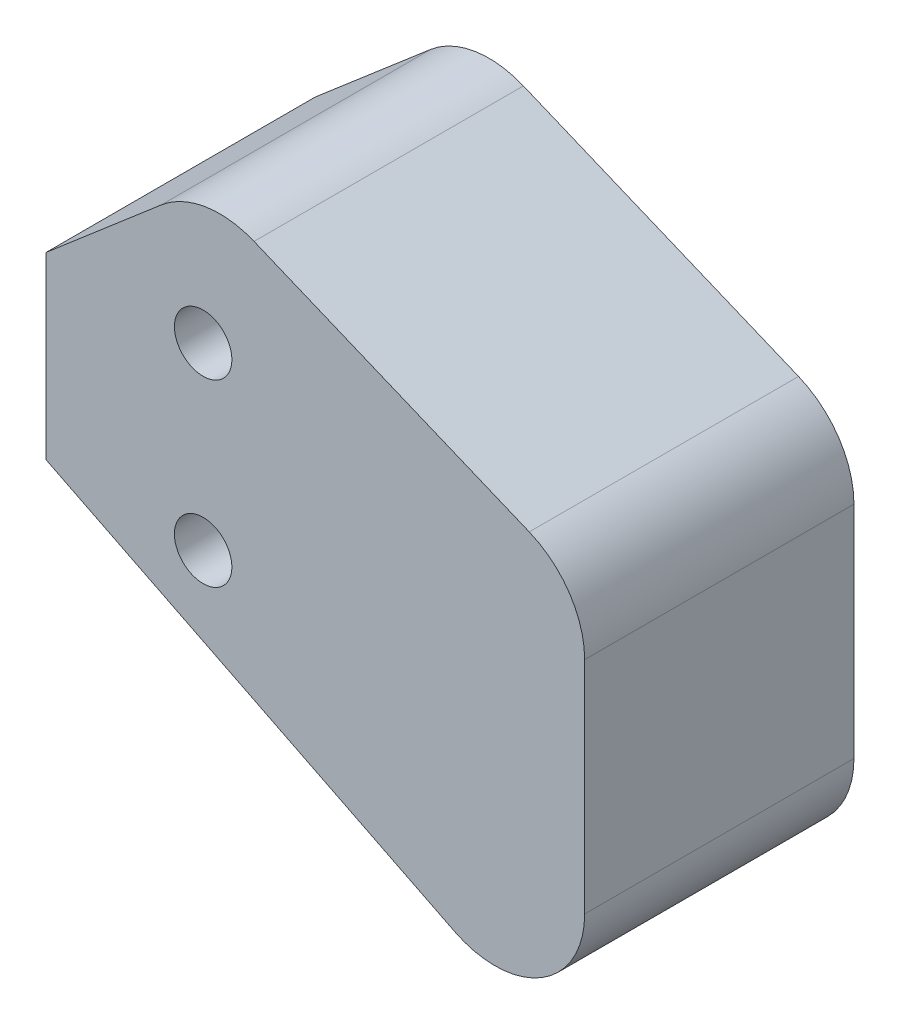
SolidWorks part; units mm, degrees
ref_plane "Front Plane" through (0, 0, 0) normal (0, 0, 1) x (1, 0, 0)
ref_plane "Top Plane" through (0, 0, 0) normal (0, 1, 0) x (1, 0, 0)
ref_plane "Right Plane" through (0, 0, 0) normal (1, 0, 0) x (0, 0, -1)
sketch "Sketch1" plane through (0, 0, 0) normal (0, 0, 1) x (1, 0, 0)
  line L0 (0, 0) -> (0, 12.7)
  line L1 (0, 12.7) -> (11.1125, 22.225)
  line L2 (0, 0) -> (38.1, -19.05)
  line L3 (11.1125, 22.225) -> (38.1, 11.0464)
  line L4 (38.1, 11.0464) -> (38.1, -19.05)
  circle A0 centre (11.1125, 12.7) radius 2.032
  circle A1 centre (11.1125, 0) radius 2.032
  point P8 (0, 0)
  point P9 (0, 0)
  point P10 (0, 0)
  point P13 (0, 0)
  point P14 (0, 14.5638)
  dimension "D3" = 4.064
  dimension "D1" = 67.5
  dimension "D2" = 38.1
  dimension "D4" = 11.1125
  dimension "D5" = 12.7
  dimension "D6" = 9.525
  dimension "D7" = 19.05
extrude "Boss-Extrude1" add sketch "Sketch1" along normal blind 19.05
fillet "Fillet1" radius 6.35 3 edges at (38.1, 11.0464, 9.525) (11.1125, 22.225, 9.525) (38.1, -19.05, 9.525)
